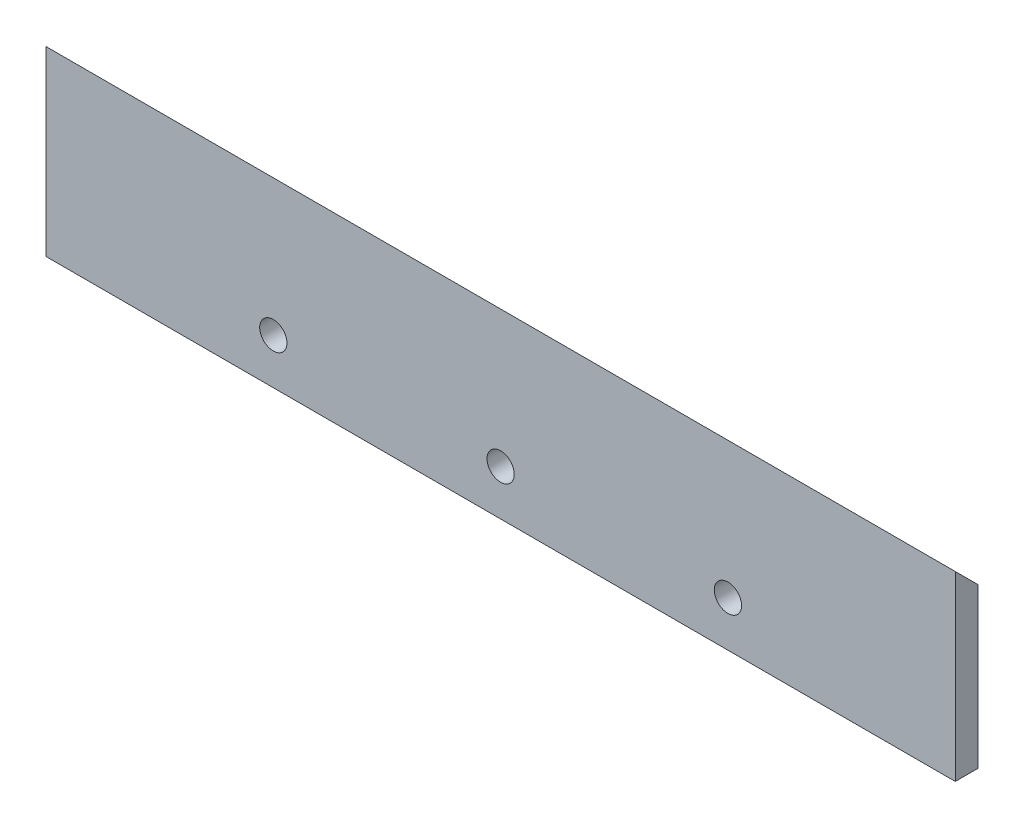
SolidWorks part; units mm, degrees
ref_plane "Front Plane" through (0, 0, 0) normal (0, 0, 1) x (1, 0, 0)
ref_plane "Top Plane" through (0, 0, 0) normal (0, 1, 0) x (1, 0, 0)
ref_plane "Right Plane" through (0, 0, 0) normal (1, 0, 0) x (0, 0, -1)
sketch "Sketch1" plane through (0, 0, 0) normal (1, 0, 0) x (0, 0, -1)
  line L1 (415.8269, -149.2325) -> (420.8269, -149.2325)
  line L2 (415.8269, -149.2325) -> (415.8269, -189.2325)
  line L3 (415.8269, -189.2325) -> (420.8269, -189.2325)
  line L4 (420.8269, -149.2325) -> (420.8269, -189.2325)
  dimension "D1" = 5
  dimension "D2" = 40
extrude "Boss-Extrude1" add sketch "Sketch1" along normal blind 200
chamfer "Chamfer1" distance 5 angle 45 1 edges at (100, -149.2325, -420.8269)
sketch "Sketch2" plane through (0, 0, -420.8269) normal (0, 0, -1) x (-1, 0, 0)
  line L0 (0, -189.2325) -> (0, -154.2325) construction
  line L1 (-200, -189.2325) -> (0, -189.2325) construction
  circle A0 centre (-50, -179.2325) radius 3
  dimension "D1" = 6
  dimension "D2" = 50
  dimension "D3" = 10
extrude "Cut-Extrude1" cut sketch "Sketch2" against normal up to surface (5 mm away) up to face at (100, -169.2325, -415.8269)
pattern_linear "LPattern1" count 3 spacing 50 along (1, 0, 0) of "Cut-Extrude1"
